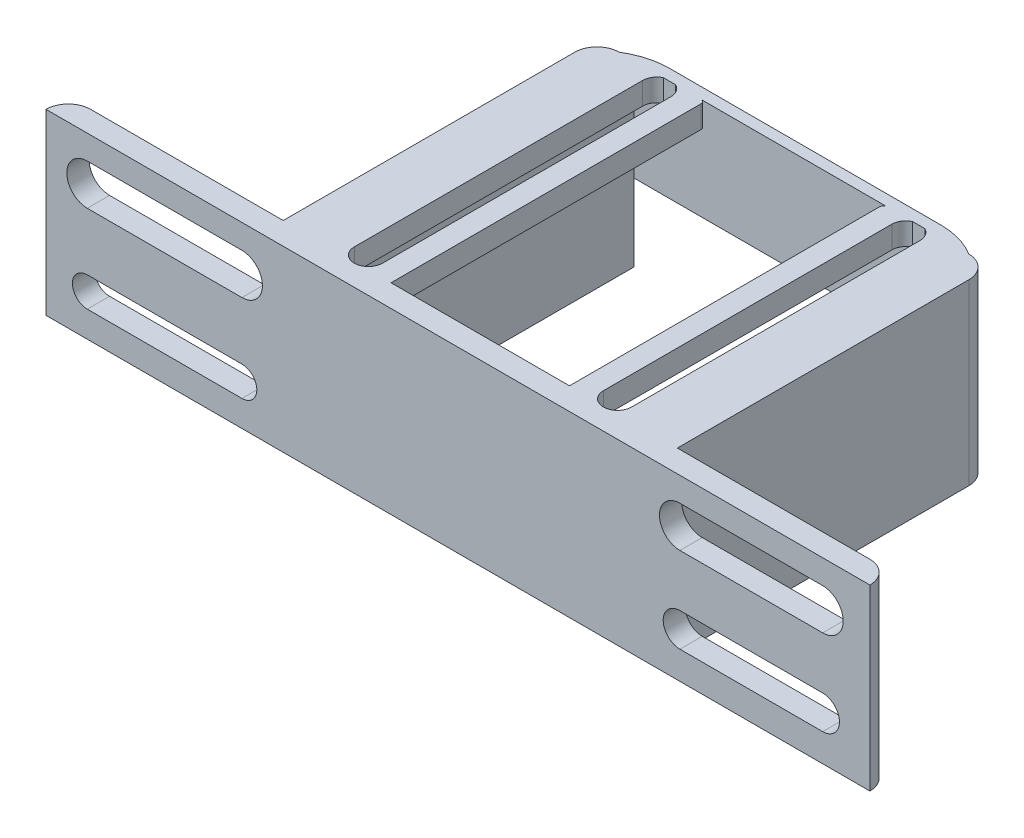
SolidWorks part; units mm, degrees
ref_plane "Front Plane" through (0, 0, 0) normal (0, 0, 1) x (1, 0, 0)
ref_plane "Top Plane" through (0, 0, 0) normal (0, 1, 0) x (1, 0, 0)
ref_plane "Right Plane" through (0, 0, 0) normal (1, 0, 0) x (0, 0, -1)
sketch "Sketch1" plane through (0, 0, 0) normal (0, 1, 0) x (1, 0, 0)
  line L0 (-55.4, 0) -> (55.4, 0)
  line L1 (55.4, 0) -> (55.4, 3)
  line L2 (55.4, 3) -> (26.5, 3)
  line L3 (26.5, 3) -> (26.5, 45.2)
  line L4 (26.5, 45.2) -> (21.5, 45.2)
  line L5 (21.5, 45.2) -> (21.5, 3)
  line L6 (21.5, 3) -> (-21.5, 3)
  line L7 (0, 0) -> (0, 100) construction
  line L9 (-55.4, 0) -> (-55.4, 3)
  line L10 (21.5, 3) -> (16.5, 3)
  line L11 (21.5, 3) -> (21.5, 45.2)
  line L12 (21.5, 45.2) -> (16.5, 45.2)
  line L13 (16.5, 3) -> (16.5, 45.2)
  line L14 (-55.4, 3) -> (-26.5, 3)
  line L15 (-26.5, 3) -> (-26.5, 45.2)
  line L16 (-26.5, 45.2) -> (-21.5, 45.2)
  line L17 (-21.5, 45.2) -> (-16.5, 45.2)
  line L18 (-21.5, 45.2) -> (-21.5, 3)
  line L19 (-16.5, 3) -> (-16.5, 45.2)
  point P20 (0, 3)
  dimension "D1" = 28.9
  dimension "D2" = 3
  dimension "D3" = 5
  dimension "D4" = 21.5
  dimension "D5" = 3
  dimension "D6" = 42.2
  dimension "D7" = 5
extrude "Boss-Extrude5" add sketch "Sketch1" along normal blind 24 contours L18 L6 L5 L4 L3 L2 L1 L0 L9 L14 L15 L16
sketch "Sketch3" plane through (0, 0, -3) normal (0, 0, -1) x (-1, 0, 0)
  line L1 (-21.5, 24) -> (-12, 24)
  line L2 (-21.5, 24) -> (-21.5, 21)
  line L3 (-21.5, 21) -> (-12, 21)
  line L4 (-12, 24) -> (-12, 21)
  line L5 (21.5, 24) -> (12, 24)
  line L6 (21.5, 24) -> (21.5, 21)
  line L7 (21.5, 21) -> (12, 21)
  line L8 (12, 24) -> (12, 21)
  dimension "D1" = 3
  dimension "D2" = 9.5
  dimension "D3" = 3
  dimension "D4" = 9.5
extrude "Boss-Extrude7" add sketch "Sketch3" along normal blind 42.2
sketch "Sketch4" plane through (0, 24, 0) normal (0, 1, 0) x (1, 0, 0)
  line L0 (12, 45.2) -> (26.5, 45.2) construction
sketch "Sketch5" plane through (0, 21, 0) normal (0, -1, 0) x (-1, 0, 0)
  line L0 (16.75, 45.2) -> (16.75, 3) construction
  line L1 (12, 45.2) -> (21.5, 45.2) construction
  line L2 (12, 3) -> (21.5, 3) construction
  line L3 (21.5, 24.1) -> (12, 24.1) construction
  line L4 (21.5, 45.2) -> (21.5, 3) construction
  line L5 (12, 45.2) -> (12, 3) construction
  line L6 (-16.75, 3) -> (-16.75, 45.2) construction
  line L7 (-21.5, 3) -> (-12, 3) construction
  line L8 (-12, 45.2) -> (-26.5, 45.2) construction
  line L9 (-16.75, 45.2) -> (-21.5, 24.1) construction
  line L10 (-21.5, 45.2) -> (-21.5, 3) construction
  line L11 (-16.75, 43.4907) -> (-16.75, 4.7093) construction
  line L12 (-14.85, 43.4907) -> (-14.85, 4.7093)
  line L13 (-18.65, 43.4907) -> (-18.65, 4.7093)
  line L14 (-16.75, 24.1) -> (16.75, 24.1) construction
  line L15 (-16.75, 2.8093) -> (19.35, 2.8093) construction
  line L16 (16.75, 4.7093) -> (16.75, 43.4907) construction
  line L17 (14.85, 4.7093) -> (14.85, 43.4907)
  line L18 (18.65, 4.7093) -> (18.65, 43.4907)
  arc A0 (-14.85, 43.4907) -> (-18.65, 43.4907) centre (-16.75, 43.4907) ccw
  arc A1 (-18.65, 4.7093) -> (-14.85, 4.7093) centre (-16.75, 4.7093) ccw
  arc A2 (14.85, 4.7093) -> (18.65, 4.7093) centre (16.75, 4.7093) ccw
  arc A3 (18.65, 43.4907) -> (14.85, 43.4907) centre (16.75, 43.4907) ccw
  point P23 (-16.75, 24.1)
  point P34 (16.75, 24.1)
extrude "Cut-Extrude3" cut sketch "Sketch5" against normal blind 42.2 contours L12 A1 L13 A0
extrude "Cut-Extrude4" cut sketch "Sketch5<4>" against normal blind 42.2 contours L18 A3 L17 A2
sketch "Sketch5<4>" plane through (0, 21, 0) normal (0, -1, 0) x (-1, 0, 0) same geometry as "Sketch5"
fillet "Fillet1" radius 3 1 edges at (-26.5, 12, -45.2)
fillet "Fillet2" radius 3 1 edges at (26.5, 12, -45.2)
fillet "Fillet3" radius 0.5 1 edges at (-12, 22.5, -45.2)
fillet "Fillet4" radius 0.5 1 edges at (12, 22.5, -45.2)
fillet "Fillet5" radius 3 1 edges at (55.4, 12, -3)
fillet "Fillet6" radius 3 1 edges at (-55.4, 12, -3)
sketch "Sketch6" plane through (0, 0, -3) normal (0, 0, -1) x (-1, 0, 0)
  line L0 (-52.4, 12) -> (-26.5, 12) construction
  line L1 (-52.4, 24) -> (-52.4, 0) construction
  line L2 (-26.5, 24) -> (-26.5, 0) construction
  line L3 (-26.5, 12) -> (-39.45, 12) construction
  line L4 (-39.45, 12) -> (-39.45, 24) construction
  line L5 (-52.4, 24) -> (-26.5, 24) construction
  line L6 (-39.45, 12) -> (-39.45, 0) construction
  line L7 (-52.4, 0) -> (-26.5, 0) construction
  line L8 (-39.45, 6) -> (-52.4, 6) construction
  line L9 (-52.4, 6) -> (-39.45, 6) construction
  line L10 (-39.45, 6) -> (-26.5, 6) construction
  line L11 (-39.45, 18) -> (-52.4, 18) construction
  line L12 (-52.4, 18) -> (-39.45, 18) construction
  line L13 (-39.45, 18) -> (-26.5, 18) construction
  line L14 (-29.85, 18) -> (-49.05, 18) construction
  line L15 (-29.85, 15.25) -> (-49.05, 15.25)
  line L16 (-29.85, 20.75) -> (-49.05, 20.75)
  line L17 (-29.85, 6) -> (-49.05, 6) construction
  line L18 (-29.85, 3.75) -> (-49.05, 3.75)
  line L19 (-29.85, 8.25) -> (-49.05, 8.25)
  arc A0 (-29.85, 15.25) -> (-29.85, 20.75) centre (-29.85, 18) ccw
  arc A1 (-49.05, 20.75) -> (-49.05, 15.25) centre (-49.05, 18) ccw
  arc A2 (-29.85, 3.75) -> (-29.85, 8.25) centre (-29.85, 6) ccw
  arc A3 (-49.05, 8.25) -> (-49.05, 3.75) centre (-49.05, 6) ccw
  point P21 (-39.45, 18)
  point P27 (-39.45, 6)
extrude "Cut-Extrude5" cut sketch "Sketch6" against normal blind 42.2
sketch "Sketch7" plane through (0, 0, -3) normal (0, 0, -1) x (-1, 0, 0)
  line L0 (26.5, 12) -> (52.4, 12) construction
  line L1 (26.5, 24) -> (26.5, 0) construction
  line L2 (52.4, 0) -> (52.4, 24) construction
  line L3 (52.4, 12) -> (52.4, 24) construction
  line L4 (39.45, 12) -> (39.45, 24) construction
  line L5 (52.4, 24) -> (26.5, 24) construction
  line L6 (39.45, 24) -> (39.45, 0) construction
  line L7 (52.4, 0) -> (26.5, 0) construction
  line L8 (26.5, 24) -> (26.5, 0) construction
  line L9 (52.4, 18) -> (26.5, 18) construction
  line L10 (39.45, 0) -> (39.45, 12) construction
  line L11 (39.45, 0) -> (39.45, 12) construction
  line L12 (26.5, 0) -> (26.5, 12) construction
  line L13 (26.5, 5.503) -> (52.4, 5.503) construction
  line L14 (29.05, 5.503) -> (49.85, 5.503) construction
  line L15 (29.05, 7.503) -> (49.85, 7.503)
  line L16 (29.05, 3.503) -> (49.85, 3.503)
  line L17 (49.85, 18) -> (29.05, 18) construction
  line L18 (49.85, 15.25) -> (29.05, 15.25)
  line L19 (49.85, 20.75) -> (29.05, 20.75)
  arc A0 (29.05, 7.503) -> (29.05, 3.503) centre (29.05, 5.503) ccw
  arc A1 (49.85, 3.503) -> (49.85, 7.503) centre (49.85, 5.503) ccw
  arc A2 (49.85, 15.25) -> (49.85, 20.75) centre (49.85, 18) ccw
  arc A3 (29.05, 20.75) -> (29.05, 15.25) centre (29.05, 18) ccw
  point P25 (39.45, 5.503)
  point P31 (39.45, 18)
extrude "Cut-Extrude6" cut sketch "Sketch7" against normal blind 42.2 contours L19 A3 L18 A2
extrude "Cut-Extrude7" cut sketch "Sketch7<3>" against normal blind 42.2 contours L15 A1 L16 A0
sketch "Sketch7<3>" plane through (0, 0, -3) normal (0, 0, -1) x (-1, 0, 0) same geometry as "Sketch7"
sketch "Sketch8" plane through (0, 0, -45.2) normal (0, 0, -1) x (-1, 0, 0)
  line L0 (-23.5, 24) -> (-23.5, 0) construction
  line L1 (23.5, 24) -> (-23.5, 24)
  line L2 (23.5, 24) -> (23.5, 10.3294)
  line L3 (23.5, 10.3294) -> (-23.5, 10.3294)
  line L4 (-23.5, 24) -> (-23.5, 10.3294)
extrude "Boss-Extrude8" add sketch "Sketch8" along normal blind 1.5
fillet "Fillet7" radius 10 2 edges at (23.5, 17.1647, -46.7) (-23.5, 17.1647, -46.7)
ref_plane "Plane1" through (55.4, 24, 0) normal (1, 0, 0) x (0, 0, -1)
